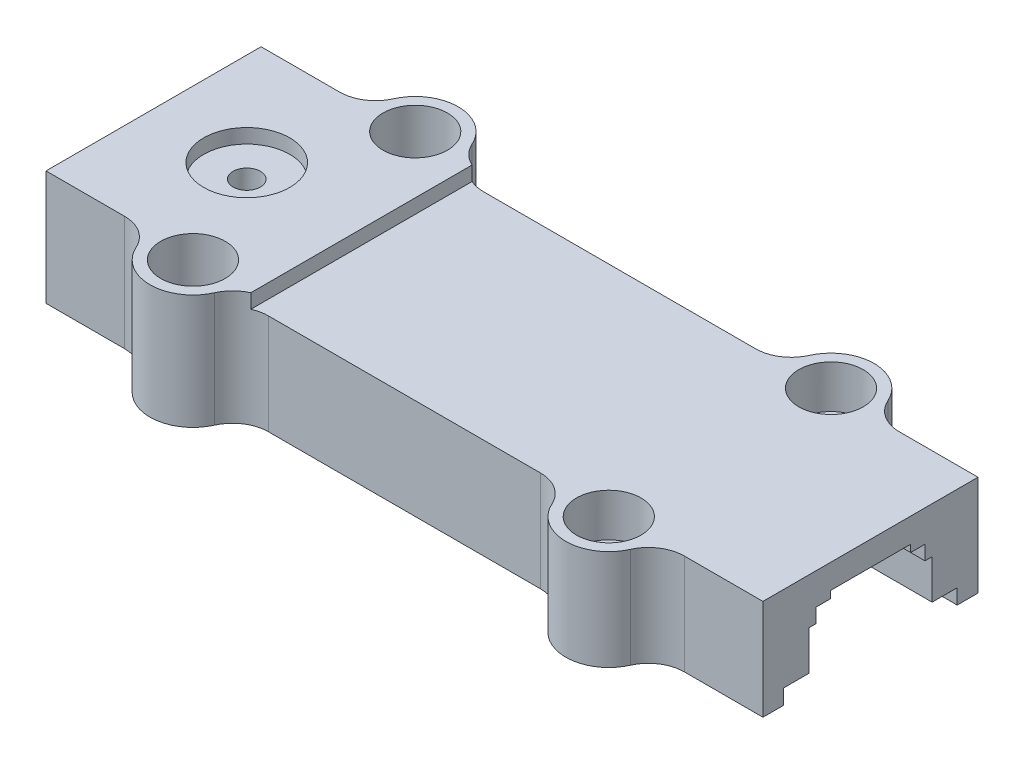
SolidWorks part; units mm, degrees
ref_plane "Front Plane" through (0, 0, 0) normal (0, 0, 1) x (1, 0, 0)
ref_plane "Top Plane" through (0, 0, 0) normal (0, 1, 0) x (1, 0, 0)
ref_plane "Right Plane" through (0, 0, 0) normal (1, 0, 0) x (0, 0, -1)
sketch "Sketch1" plane through (0, 0, 0) normal (0, 1, 0) x (1, 0, 0)
  line L1 (0, 15) -> (100, 15)
  line L2 (0, 15) -> (0, -15)
  line L3 (0, -15) -> (100, -15)
  line L4 (100, 15) -> (100, -15)
  point P4 (0, 0)
  dimension "D1" = 30
  dimension "D2" = 100
extrude "Boss-Extrude1" add sketch "Sketch1" along normal blind 16
sketch "Sketch2" plane through (100, 0, 0) normal (1, 0, 0) x (0, 0, -1)
  line L1 (-7.6, 0) -> (7.6, 0)
  line L2 (-7.6, 0) -> (-7.6, 9.6)
  line L3 (-7.6, 9.6) -> (7.6, 9.6)
  line L4 (7.6, 0) -> (7.6, 9.6)
  point P4 (0, 0)
  dimension "D1" = 15.2
  dimension "D2" = 9.6
extrude "Cut-Extrude1" cut sketch "Sketch2" against normal through all
sketch "Sketch3" plane through (100, 0, 0) normal (1, 0, 0) x (0, 0, -1)
  line L0 (-15, 16) -> (-15, 0) construction
  line L1 (-7.6, 0) -> (-12.1, 0)
  line L2 (-7.6, 0) -> (-7.6, 2.1)
  line L3 (-7.6, 2.1) -> (-12.1, 2.1)
  line L4 (-12.1, 0) -> (-12.1, 2.1)
  line L5 (7.6, 0) -> (15, 0) construction
  line L6 (12.1, 0) -> (7.6, 0)
  line L7 (12.1, 0) -> (12.1, 2.1)
  line L8 (12.1, 2.1) -> (7.6, 2.1)
  line L9 (7.6, 0) -> (7.6, 2.1)
  line L10 (7.6, 0) -> (7.6, 9.6) construction
  line L11 (15, 16) -> (15, 0) construction
  line L12 (7.6, 9.6) -> (-7.6, 9.6) construction
  line L13 (-7.6, 2.1) -> (-8.6, 2.1)
  line L14 (-7.6, 2.1) -> (-7.6, 7.6)
  line L15 (-7.6, 7.6) -> (-8.6, 7.6)
  line L16 (-8.6, 2.1) -> (-8.6, 7.6)
  line L17 (-7.6, 9.6) -> (-7.6, 0) construction
  line L18 (7.6, 2.1) -> (8.6, 2.1)
  line L19 (7.6, 2.1) -> (7.6, 7.6)
  line L20 (7.6, 7.6) -> (8.6, 7.6)
  line L21 (8.6, 2.1) -> (8.6, 7.6)
  line L22 (-5.6, 9.6) -> (5.6, 9.6)
  line L23 (-5.6, 9.6) -> (-5.6, 10.6)
  line L24 (-5.6, 10.6) -> (5.6, 10.6)
  line L25 (5.6, 9.6) -> (5.6, 10.6)
  line M1 (-15, 0) -> (-7.6, 0)
  line M2 (-7.6, 0) -> (-7.6, 9.6)
  line M3 (-7.6, 9.6) -> (7.6, 9.6)
  line M4 (7.6, 9.6) -> (7.6, 0)
  line M5 (7.6, 0) -> (15, 0)
  dimension "D1" = 2.1
  dimension "D2" = 2.9
  dimension "D3" = 2.9
  dimension "D4" = 2.1
  dimension "D5" = 1
  dimension "D6" = 2
  dimension "D7" = 1
  dimension "D8" = 2
  dimension "D9" = 1
  dimension "D10" = 2
  dimension "D11" = 2
extrude "Cut-Extrude2" cut sketch "Sketch3" against normal through all contours L16 L3 L15 M2 | L8 L21 L20 M4 | L7 L8 M4 M5 | L4 L3 M1 M2 | L25 L24 L23 M3 region at (100, 4.85, -8.1) region at (100, 10.1, 0) region at (100, 1.05, 9.85) region at (100, 4.85, 8.1) region at (100, 1.05, -9.85)
sketch "Sketch4" plane through (0, 0, 0) normal (0, -1, 0) x (1, 0, 0)
  line L0 (0, 12.1) -> (100, 12.1) construction
  line L1 (0, -12.1) -> (5, -12.1)
  line L2 (0, -12.1) -> (0, 12.1)
  line L3 (0, 12.1) -> (5, 12.1)
  line L4 (5, -12.1) -> (5, 12.1)
  dimension "D1" = 5
extrude "Boss-Extrude2" add sketch "Sketch4" against normal up to next
sketch "Sketch6" plane through (0, 0, 0) normal (0, -1, 0) x (1, 0, 0)
  line L0 (5, -12.1) -> (100, -12.1) construction
  line L1 (5, 12.1) -> (2.9, 12.1)
  line L2 (5, 12.1) -> (5, -12.1)
  line L3 (5, -12.1) -> (2.9, -12.1)
  line L4 (2.9, 12.1) -> (2.9, -12.1)
  line L5 (0, -15) -> (0, 15) construction
  dimension "D1" = 2.9
extrude "Cut-Extrude3" cut sketch "Sketch6" against normal up to surface (2.1 mm away) up to face at (52.5, 2.1, 10.35)
sketch "Sketch9" plane through (0, 9.6, 0) normal (0, -1, 0) x (1, 0, 0)
  line L0 (5, -5.6) -> (100, -5.6) construction
  line L1 (5, 5.6) -> (24.05, 5.6)
  line L2 (5, 5.6) -> (5, -5.6)
  line L3 (5, -5.6) -> (24.05, -5.6)
  line L4 (24.05, 5.6) -> (24.05, -5.6)
  dimension "D1" = 19.05
extrude "Boss-Extrude3" add sketch "Sketch9" against normal up to next
fillet "Fillet1" radius 1.5875 4 edges at (5, 4.85, -8.6) (5, 4.85, 8.6) (2.9, 1.05, -12.1) (2.9, 1.05, 12.1)
fillet "Fillet2" radius 1.5875 2 edges at (5.1127, 8.6, -7.6) (5.1127, 8.6, 7.6)
sketch "Sketch7" plane through (0, 9.6, 0) normal (0, -1, 0) x (1, 0, 0)
  line L1 (5, -6.0125) -> (5, 6.0125) construction
  circle A0 centre (13, 0) radius 1.905
  dimension "D1" = 3.81
  dimension "D2" = 8
extrude "Cut-Extrude4" cut sketch "Sketch7" against normal through all
sketch "Sketch10" plane through (0, 9.6, 0) normal (0, -1, 0) x (1, 0, 0)
  circle A0 centre (13, 0) radius 3.25
  circle A3 centre (13, 0) radius 1.905 construction
  dimension "D1" = 6.5
extrude "Cut-Extrude6" cut sketch "Sketch10" against normal blind 1
sketch "Sketch8" plane through (0, 16, 0) normal (0, 1, 0) x (1, 0, 0)
  circle A0 centre (13, 0) radius 6
  dimension "D1" = 12
extrude "Cut-Extrude5" cut sketch "Sketch8" against normal blind 2
fillet "Fillet5" radius 1.5875 2 edges at (24.05, 10.1, -5.6) (24.05, 10.1, 5.6)
sketch "Sketch11" plane through (0, 16, 0) normal (0, 1, 0) x (1, 0, 0)
  line L4 (27, -15.5) -> (27, -15)
  line L5 (15, -15) -> (15, -15.5)
  line L6 (73, -15) -> (73, -15.5)
  line L7 (85, -15.5) -> (85, -15)
  line L8 (15, -15) -> (27, -15)
  line L9 (73, -15) -> (85, -15)
  line L11 (0, 15) -> (0, -15) construction
  line L12 (100, -15) -> (100, 15) construction
  line L13 (0, -15) -> (100, -15) construction
  arc A2 (15, -15.5) -> (27, -15.5) centre (21, -15.5) ccw
  arc A3 (73, -15.5) -> (85, -15.5) centre (79, -15.5) ccw
  dimension "D1" = 15
  dimension "D2" = 12
  dimension "D3" = 15
  dimension "D4" = 12
  dimension "D5" = 0.5
extrude "Boss-Extrude4" add sketch "Sketch11" against normal up to surface (16 mm away) up to face at (41.4117, 0, 0)
sketch "Sketch12" plane through (0, 16, 0) normal (0, 1, 0) x (1, 0, 0)
  circle A0 centre (21, -15.5) radius 4.5
  circle A1 centre (79, -15.5) radius 4.5
  dimension "D1" = 9
extrude "Cut-Extrude7" cut sketch "Sketch12" against normal blind 8
sketch "Sketch13" plane through (0, 8, 0) normal (0, 1, 0) x (1, 0, 0)
  circle A0 centre (21, -15.5) radius 2.75
  circle A1 centre (79, -15.5) radius 2.75
  dimension "D1" = 5.5
extrude "Cut-Extrude8" cut sketch "Sketch13" against normal through all
mirror "Mirror1" about plane through (0, 0, 0) normal (0, 0, 1) of "Boss-Extrude4", "Cut-Extrude7", "Cut-Extrude8"
fillet "Fillet6" radius 5 8 edges at (73, 8, 15) (85, 8, 15) (85, 8, -15) (73, 8, -15)
sketch "Sketch18" plane through (0, 0, 0) normal (0, 0, 1) x (1, 0, 0)
  line L0 (110.1874, 14) -> (39, 14)
  line L1 (26.475, 16) -> (15.525, 16) construction
  line L2 (19, 14) -> (19, 16) construction
  line L3 (89.0374, 0) -> (100, 0) construction
  line L4 (110.1874, 14) -> (110.1874, 34.8426)
  line L5 (110.1874, 34.8426) -> (29, 34.8426)
  line L6 (29, 34.8426) -> (29, 16)
  line L7 (29, 16) -> (29, 14)
  line L8 (29, 14) -> (39, 14)
  arc A0 (39, 14) -> (29, 16) centre (39, 40) cw construction
  dimension "D1" = 10
  dimension "D2" = 10
  dimension "D3" = 14
extrude "Cut-Extrude9" cut sketch "Sketch18" against normal mid plane 100
sketch "Sketch14" plane through (0, 0, 0) normal (0, -1, 0) x (1, 0, 0)
  line L0 (100, 15) -> (100, 12.1) construction
  line L1 (100, -21.5) -> (-10, -21.5)
  line L2 (100, -21.5) -> (100, 55.5)
  line L3 (100, 55.5) -> (-10, 55.5)
  line L4 (-10, -21.5) -> (-10, 55.5)
  arc A0 (73.525, -17.9545) -> (84.475, -17.9545) centre (79, -15.5) ccw construction
  dimension "D1" = 77
  dimension "D2" = 110
sketch "Sketch15" plane through (0, 2.1, 0) normal (0, -1, 0) x (1, 0, 0)
  line L0 (6.5875, 8.6) -> (100, 8.6) construction
  line L1 (5, 6.0125) -> (5, 7.0125) construction
  line L2 (5, -7.0125) -> (5, -6.0125) construction
  line L3 (6.5875, -8.6) -> (100, -8.6) construction
  line L4 (6.5875, 8.6) -> (100, 8.6)
  line L5 (5, 6.0125) -> (5, 7.0125)
  line L6 (5, -7.0125) -> (5, -6.0125)
  line L7 (6.5875, -8.6) -> (100, -8.6)
  line L8 (5, 6.0125) -> (5, -6.0125)
  arc A0 (6.5875, 8.6) -> (5, 7.0125) centre (6.5875, 7.0125) ccw construction
  arc A1 (5, -7.0125) -> (6.5875, -8.6) centre (6.5875, -7.0125) ccw construction
  arc A2 (6.5875, 8.6) -> (5, 7.0125) centre (6.5875, 7.0125) ccw
  arc A3 (5, -7.0125) -> (6.5875, -8.6) centre (6.5875, -7.0125) ccw
sketch "Sketch16" plane through (0, 9.6, 0) normal (0, -1, 0) x (1, 0, 0)
  line L0 (25.6375, 5.6) -> (100, 5.6) construction
  line L1 (25.6375, 5.6) -> (100, 5.6)
  line L2 (24.05, -4.0125) -> (24.05, 4.0125) construction
  line L3 (25.6375, -5.6) -> (100, -5.6) construction
  line L4 (24.05, -4.0125) -> (24.05, 4.0125)
  line L5 (25.6375, -5.6) -> (100, -5.6)
  arc A0 (25.6375, 5.6) -> (24.05, 4.0125) centre (25.6375, 4.0125) ccw construction
  arc A1 (24.05, -4.0125) -> (25.6375, -5.6) centre (25.6375, -4.0125) ccw construction
  arc A2 (25.6375, 5.6) -> (24.05, 4.0125) centre (25.6375, 4.0125) ccw
  arc A3 (24.05, -4.0125) -> (25.6375, -5.6) centre (25.6375, -4.0125) ccw
sketch "Sketch17" plane through (0, 7.6, 0) normal (0, -1, 0) x (1, 0, 0)
  line L0 (6.5875, -7.6) -> (100, -7.6) construction
  line L1 (6.5875, 7.6) -> (100, 7.6) construction
  line L2 (6.5875, -7.6) -> (100, -7.6)
  line L3 (6.5875, 7.6) -> (100, 7.6)
  line L4 (5, 6.0125) -> (5, -6.0125)
  arc A0 (5, -6.0125) -> (6.5875, -7.6) centre (6.5875, -6.0125) ccw construction
  arc A1 (6.5875, 7.6) -> (5, 6.0125) centre (6.5875, 6.0125) ccw construction
  arc A2 (5, -6.0125) -> (6.5875, -7.6) centre (6.5875, -6.0125) ccw
  arc A3 (6.5875, 7.6) -> (5, 6.0125) centre (6.5875, 6.0125) ccw
sketch "Sketch20" plane through (0, 16, 0) normal (0, 1, 0) x (1, 0, 0)
  line L0 (0, 15) -> (0, -15) construction
  line L1 (0, -15) -> (10.9626, -15) construction
  line L2 (68.9626, -15) -> (31.0374, -15) construction
  line L3 (100, -15) -> (89.0374, -15) construction
  line L4 (100, 15) -> (100, -15) construction
  line L5 (89.0374, 15) -> (100, 15) construction
  line L6 (31.0374, 15) -> (68.9626, 15) construction
  line L7 (10.9626, 15) -> (0, 15) construction
  line L8 (0, 15) -> (0, -15)
  line L9 (0, -15) -> (10.9626, -15)
  line L10 (68.9626, -15) -> (31.0374, -15)
  line L11 (100, -15) -> (89.0374, -15)
  line L12 (100, 15) -> (100, -15)
  line L13 (89.0374, 15) -> (100, 15)
  line L14 (31.0374, 15) -> (68.9626, 15)
  line L15 (10.9626, 15) -> (0, 15)
  arc A0 (15.525, -17.9545) -> (10.9626, -15) centre (10.9626, -20) ccw construction
  arc A1 (15.525, -17.9545) -> (26.475, -17.9545) centre (21, -15.5) ccw construction
  arc A2 (29, -15.4339) -> (26.475, -17.9545) centre (31.0374, -20) ccw construction
  arc A3 (31.0374, -15) -> (29, -15.4339) centre (31.0374, -20) ccw construction
  arc A4 (73.525, -17.9545) -> (68.9626, -15) centre (68.9626, -20) ccw construction
  arc A5 (73.525, -17.9545) -> (84.475, -17.9545) centre (79, -15.5) ccw construction
  arc A6 (89.0374, -15) -> (84.475, -17.9545) centre (89.0374, -20) ccw construction
  arc A7 (84.475, 17.9545) -> (89.0374, 15) centre (89.0374, 20) ccw construction
  arc A8 (84.475, 17.9545) -> (73.525, 17.9545) centre (79, 15.5) ccw construction
  arc A9 (68.9626, 15) -> (73.525, 17.9545) centre (68.9626, 20) ccw construction
  arc A10 (29, 15.4339) -> (31.0374, 15) centre (31.0374, 20) ccw construction
  arc A11 (26.475, 17.9545) -> (29, 15.4339) centre (31.0374, 20) ccw construction
  arc A12 (26.475, 17.9545) -> (15.525, 17.9545) centre (21, 15.5) ccw construction
  arc A13 (10.9626, 15) -> (15.525, 17.9545) centre (10.9626, 20) ccw construction
  arc A14 (15.525, -17.9545) -> (10.9626, -15) centre (10.9626, -20) ccw
  arc A15 (15.525, -17.9545) -> (26.475, -17.9545) centre (21, -15.5) ccw
  arc A16 (29, -15.4339) -> (26.475, -17.9545) centre (31.0374, -20) ccw
  arc A17 (31.0374, -15) -> (29, -15.4339) centre (31.0374, -20) ccw
  arc A18 (73.525, -17.9545) -> (68.9626, -15) centre (68.9626, -20) ccw
  arc A19 (73.525, -17.9545) -> (84.475, -17.9545) centre (79, -15.5) ccw
  arc A20 (89.0374, -15) -> (84.475, -17.9545) centre (89.0374, -20) ccw
  arc A21 (84.475, 17.9545) -> (89.0374, 15) centre (89.0374, 20) ccw
  arc A22 (84.475, 17.9545) -> (73.525, 17.9545) centre (79, 15.5) ccw
  arc A23 (68.9626, 15) -> (73.525, 17.9545) centre (68.9626, 20) ccw
  arc A24 (29, 15.4339) -> (31.0374, 15) centre (31.0374, 20) ccw
  arc A25 (26.475, 17.9545) -> (29, 15.4339) centre (31.0374, 20) ccw
  arc A26 (26.475, 17.9545) -> (15.525, 17.9545) centre (21, 15.5) ccw
  arc A27 (10.9626, 15) -> (15.525, 17.9545) centre (10.9626, 20) ccw
sketch "Sketch21" plane through (0, 16, 0) normal (0, 1, 0) x (1, 0, 0)
  line L0 (0, -15) -> (10.9626, -15) construction
  line L1 (0, -4.2181) -> (0, -15)
  line L3 (9.7824, -15) -> (10.9626, -15)
  line L5 (47.8521, -15) -> (68.9626, -15)
  line L7 (99.038, -15) -> (100, -15)
  line L8 (10.9626, 15) -> (0, 15)
  line L9 (0, 15) -> (0, -15)
  line L10 (0, -15) -> (10.9626, -15)
  line L11 (31.0374, -15) -> (68.9626, -15)
  line L12 (89.0374, -15) -> (100, -15)
  line L13 (100, -15) -> (100, 15)
  line L14 (100, 15) -> (89.0374, 15)
  line L15 (68.9626, 15) -> (31.0374, 15)
  line L16 (10.9626, 15) -> (0, 15)
  line L17 (0, 15) -> (0, 3.7819)
  line L18 (0, -15) -> (1.7824, -15)
  line L19 (31.0374, -15) -> (39.8521, -15)
  line L20 (89.0374, -15) -> (91.038, -15)
  line L21 (100, -15) -> (100, 15)
  line L22 (100, 15) -> (89.0374, 15)
  line L23 (68.9626, 15) -> (31.0374, 15)
  arc A14 (15.525, -17.9545) -> (10.9626, -15) centre (10.9626, -20) ccw
  arc A15 (15.525, -17.9545) -> (26.475, -17.9545) centre (21, -15.5) ccw
  arc A16 (29, -15.4339) -> (26.475, -17.9545) centre (31.0374, -20) ccw
  arc A17 (31.0374, -15) -> (29, -15.4339) centre (31.0374, -20) ccw
  arc A18 (73.525, -17.9545) -> (68.9626, -15) centre (68.9626, -20) ccw
  arc A19 (73.525, -17.9545) -> (84.475, -17.9545) centre (79, -15.5) ccw
  arc A20 (89.0374, -15) -> (84.475, -17.9545) centre (89.0374, -20) ccw
  arc A21 (84.475, 17.9545) -> (89.0374, 15) centre (89.0374, 20) ccw
  arc A22 (84.475, 17.9545) -> (73.525, 17.9545) centre (79, 15.5) ccw
  arc A23 (68.9626, 15) -> (73.525, 17.9545) centre (68.9626, 20) ccw
  arc A24 (29, 15.4339) -> (31.0374, 15) centre (31.0374, 20) ccw
  arc A25 (26.475, 17.9545) -> (29, 15.4339) centre (31.0374, 20) ccw
  arc A26 (26.475, 17.9545) -> (15.525, 17.9545) centre (21, 15.5) ccw
  arc A27 (10.9626, 15) -> (15.525, 17.9545) centre (10.9626, 20) ccw
  arc A28 (15.525, -17.9545) -> (10.9626, -15) centre (10.9626, -20) ccw
  arc A29 (15.525, -17.9545) -> (26.475, -17.9545) centre (21, -15.5) ccw
  arc A30 (29, -15.4339) -> (26.475, -17.9545) centre (31.0374, -20) ccw
  arc A31 (31.0374, -15) -> (29, -15.4339) centre (31.0374, -20) ccw
  arc A32 (73.525, -17.9545) -> (68.9626, -15) centre (68.9626, -20) ccw
  arc A33 (73.525, -17.9545) -> (84.475, -17.9545) centre (79, -15.5) ccw
  arc A34 (89.0374, -15) -> (84.475, -17.9545) centre (89.0374, -20) ccw
  arc A35 (84.475, 17.9545) -> (89.0374, 15) centre (89.0374, 20) ccw
  arc A36 (84.475, 17.9545) -> (73.525, 17.9545) centre (79, 15.5) ccw
  arc A37 (68.9626, 15) -> (73.525, 17.9545) centre (68.9626, 20) ccw
  arc A38 (29, 15.4339) -> (31.0374, 15) centre (31.0374, 20) ccw
  arc A39 (26.475, 17.9545) -> (29, 15.4339) centre (31.0374, 20) ccw
  arc A40 (26.475, 17.9545) -> (15.525, 17.9545) centre (21, 15.5) ccw
  arc A41 (10.9626, 15) -> (15.525, 17.9545) centre (10.9626, 20) ccw
  dimension "D2" = 8
  dimension "D3" = 8
  dimension "D4" = 8
  dimension "D5" = 8
  dimension "D1" = 0
sketch "Sketch22" plane through (0, 16, 0) normal (0, 1, 0) x (1, 0, 0)
  line L0 (0, 15) -> (0, 10.8097)
  line L2 (0, 15) -> (0, -15) construction
  line L3 (0, 15) -> (5.4813, 15)
  line L4 (10.9626, 15) -> (0, 15) construction
sketch "Sketch23" plane through (0, 14, 0) normal (0, 1, 0) x (1, 0, 0)
  line L0 (29, -21.5) -> (29, 21.5)
  line L1 (29, 21.5) -> (100, 21.5)
  line L2 (100, 21.5) -> (100, -21.5)
  line L3 (100, -21.5) -> (29, -21.5)
  line L4 (29, 15.4339) -> (29, -15.4339) construction
  line L5 (100, 15) -> (100, -15) construction
  arc A0 (84.475, 17.9545) -> (73.525, 17.9545) centre (79, 15.5) ccw construction
  arc A1 (73.525, -17.9545) -> (84.475, -17.9545) centre (79, -15.5) ccw construction
